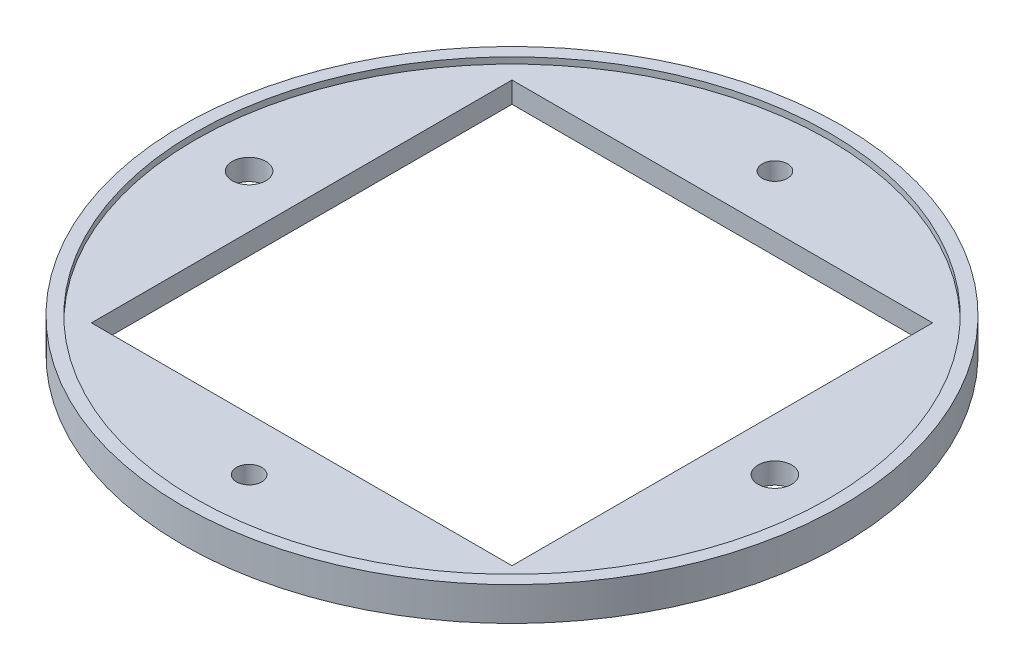
SolidWorks part; units mm, degrees
material "Custom Plastic"
ref_plane "Front Plane" through (0, 0, 0) normal (0, 0, 1) x (1, 0, 0)
ref_plane "Top Plane" through (0, 0, 0) normal (0, 1, 0) x (1, 0, 0)
ref_plane "Right Plane" through (0, 0, 0) normal (1, 0, 0) x (0, 0, -1)
sketch "Sketch1" plane through (0, 0, 0) normal (0, 1, 0) x (1, 0, 0)
  line L0 (0, 0) -> (0, -17.9724) construction
  line L1 (-50, -50) -> (50, -50)
  line L2 (-50, -50) -> (-50, 50)
  line L3 (-50, 50) -> (50, 50)
  line L4 (50, -50) -> (50, 50)
  line L5 (-50, -50) -> (50, 50) construction
  line L6 (-50, 50) -> (50, -50) construction
  line L7 (0, 0) -> (14.9739, 0) construction
  line L8 (0, 62.5) -> (14.3316, 62.5) construction
  line L9 (0, 78.35) -> (25.822, 78.35) construction
  circle A0 centre (0, 0) radius 78.35
  circle A1 centre (0, 0) radius 62.5 construction
  circle A3 centre (62.5, 0) radius 4
  circle A5 centre (-62.5, 0) radius 4
  circle A6 centre (0, 62.5) radius 3
  circle A7 centre (0, -62.5) radius 3
  dimension "D1" = 156.7
  dimension "D4" = 125
  dimension "D5" = 8
  dimension "D6" = 6
  dimension "D7" = 6
  dimension "D2" = 100
  dimension "D3" = 100
extrude "Boss-Extrude1" add sketch "Sketch1" along normal blind 2.5 and the other way blind 2.5
sketch "Sketch2" plane through (0, 0, 0) normal (0, 1, 0) x (1, 0, 0)
  circle A0 centre (0, 0) radius 78.35 construction
  circle A1 centre (0, 0) radius 78.35
  circle A2 centre (0, 0) radius 75.35
  dimension "D1" = 3
extrude "Boss-Extrude2" add sketch "Sketch2" along normal blind 4 and the other way blind 4
